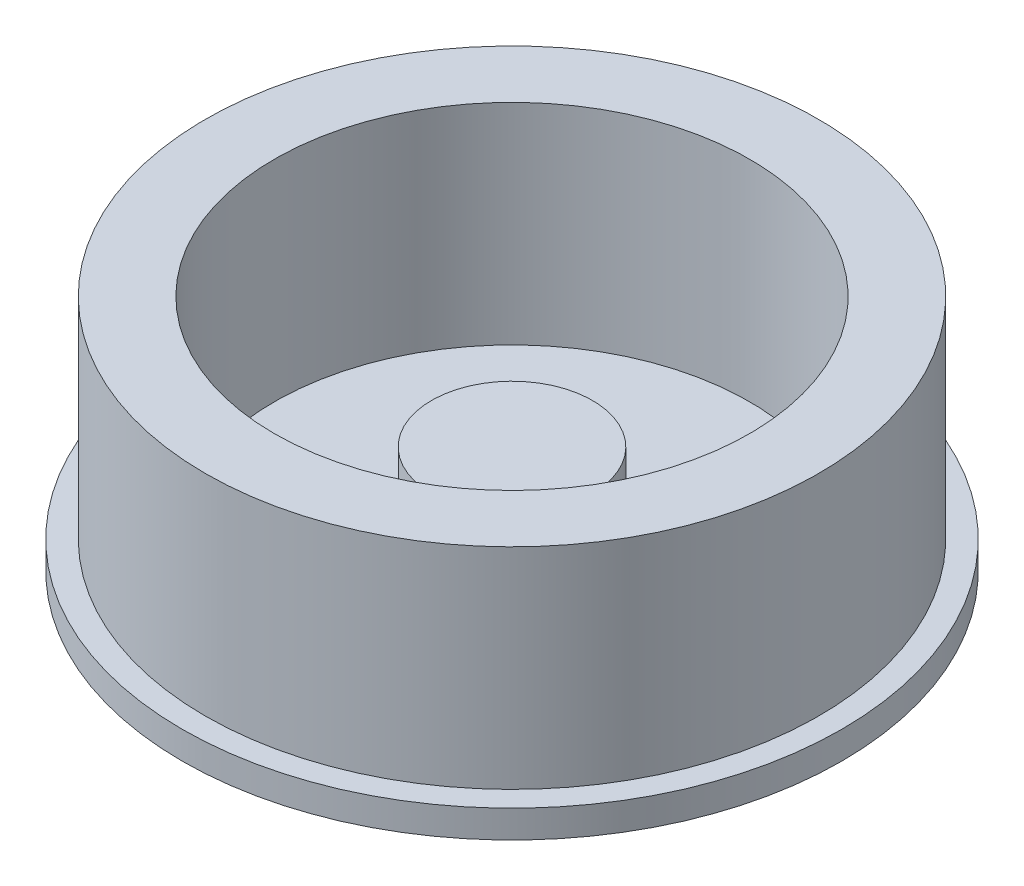
SolidWorks part; units mm, degrees
ref_plane "前视基准面" through (0, 0, 0) normal (0, 0, 1) x (1, 0, 0)
ref_plane "上视基准面" through (0, 0, 0) normal (0, 1, 0) x (1, 0, 0)
ref_plane "右视基准面" through (0, 0, 0) normal (1, 0, 0) x (0, 0, -1)
other "Configuration Table"
sketch "01_Bowl_Flange_Profile" plane through (0, 0, 0) normal (0, 1, 0) x (1, 0, 0)
  circle A0 centre (0, 0) radius 215
  circle A1 centre (170.9177, 70.7964) radius 6
  circle A2 centre (70.7964, 170.9177) radius 6
  circle A3 centre (-70.7964, 170.9177) radius 6
  circle A4 centre (-170.9177, 70.7964) radius 6
  circle A5 centre (-170.9177, -70.7964) radius 6
  circle A6 centre (-70.7964, -170.9177) radius 6
  circle A7 centre (70.7964, -170.9177) radius 6
  circle A8 centre (170.9177, -70.7964) radius 6
extrude "01_Bowl_Base_Flange" add sketch "01_Bowl_Flange_Profile" along normal blind 18
sketch "02_Bowl_Wall_Profile" plane through (0, 0, 0) normal (0, 1, 0) x (1, 0, 0)
  circle A0 centre (0, 0) radius 200
  circle A1 centre (0, 0) radius 155
extrude "02_Bowl_Wall" add sketch "02_Bowl_Wall_Profile" along normal blind 155
sketch "03_Center_Cone_Base" plane through (0, 0, 0) normal (0, 1, 0) x (1, 0, 0)
  circle A0 centre (0, 0) radius 52.5
extrude "03_Center_Guide_Boss" add sketch "03_Center_Cone_Base" along normal blind 70
